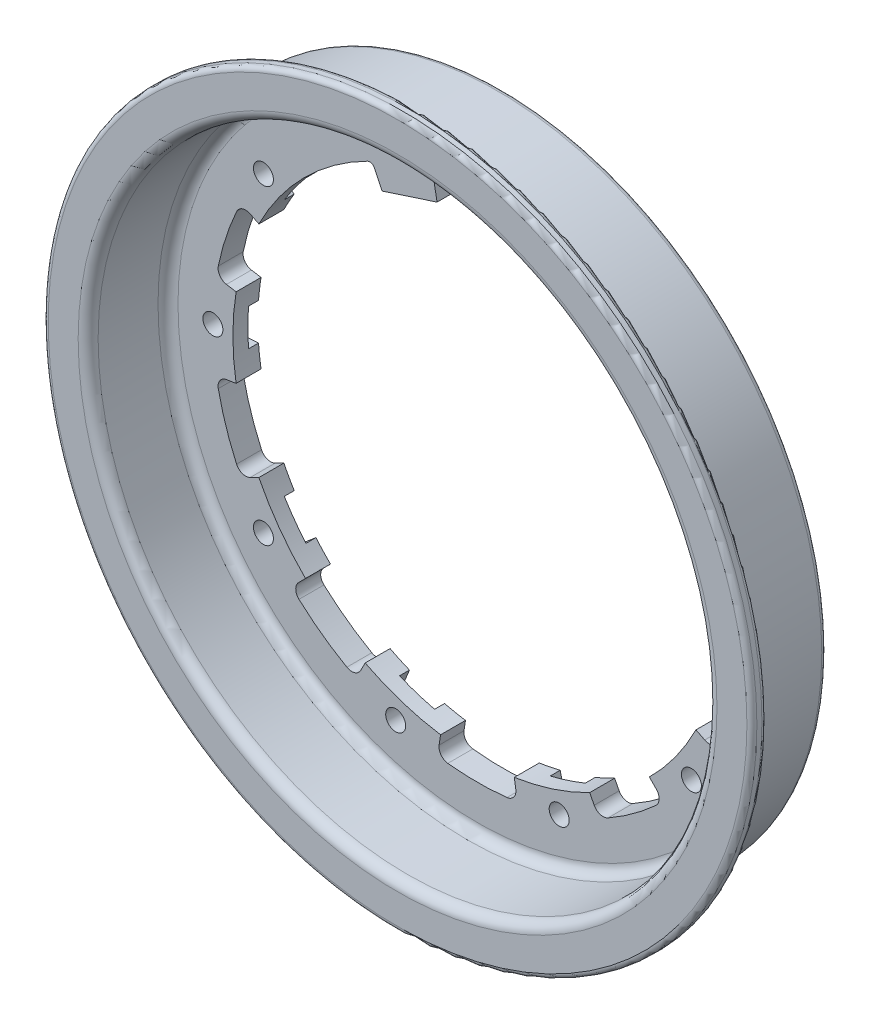
SolidWorks part; units mm, degrees
material "6061 合金"
ref_plane "前视基准面" through (0, 0, 0) normal (0, 0, 1) x (1, 0, 0)
ref_plane "上视基准面" through (0, 0, 0) normal (0, 1, 0) x (1, 0, 0)
ref_plane "右视基准面" through (0, 0, 0) normal (1, 0, 0) x (0, 0, -1)
sketch "草图2" plane through (0, 0, 0) normal (0, 0, 1) x (1, 0, 0)
  circle A0 centre (0, 0) radius 65 construction
  circle A1 centre (0, 0) radius 65 construction
  circle A2 centre (0, 0) radius 71
  circle A4 centre (0, 0) radius 62
  dimension "D1" = 6
  dimension "D3" = 3
extrude "凸台-拉伸1" add sketch "草图2" along normal blind 3
sketch "草图3" plane through (0, 0, 0) normal (0, 0, -1) x (-1, 0, 0)
  circle A0 centre (0, 0) radius 65 construction
  circle A1 centre (0, 0) radius 62 construction
  circle A2 centre (0, 0) radius 65
  circle A3 centre (0, 0) radius 62
  circle M3 centre (0, 0) radius 62
extrude "凸台-拉伸2" add sketch "草图3" along normal offset from surface (16 mm away) 3 contours A2 M3 region at (63.1615, 0, 0) offset beyond the face yes
sketch "草图4" plane through (0, 0, -13) normal (0, 0, -1) x (-1, 0, 0)
  circle A0 centre (0, 0) radius 53 construction
  circle A2 centre (0, 0) radius 65 construction
  circle A3 centre (0, 0) radius 65
  circle A4 centre (0, 0) radius 49
extrude "凸台-拉伸3" add sketch "草图4" along normal blind 5
fillet "圆角1" radius 2 1 edges at (-62, 0, -13)
fillet "圆角3" radius 2 1 edges at (62, 0, 3)
fillet "圆角4" radius 1 2 edges at (71, 0, 0) (71, 0, 3)
sketch "草图5" plane through (0, 0, 3) normal (0, 0, 1) x (1, 0, 0)
  circle A0 centre (42.8779, 31.1526) radius 2
  circle A1 centre (53, 0) radius 2
  circle A2 centre (42.8779, -31.1526) radius 2
  circle A3 centre (16.3779, -50.406) radius 2
  circle A4 centre (-16.3779, -50.406) radius 2
  circle A5 centre (-42.8779, -31.1526) radius 2
  circle A6 centre (-53, 0) radius 2
  circle A7 centre (-42.8779, 31.1526) radius 2
  circle A8 centre (-16.3779, 50.406) radius 2
  circle A9 centre (16.3779, 50.406) radius 2
  point P24 (0, 0)
  dimension "D1" = 10
extrude "切除-拉伸1" cut sketch "草图5" against normal through all both and the other way through all
ref_axis "基准轴1" through (-16.3779, 50.406, -18) along (0, 0, 1)
ref_axis "基准轴2" through (16.3779, -50.406, -18) along (0, 0, 1)
ref_plane "基准面1" through (0, 0, 0) normal (-0.9511, -0.309, 0) x (0, 0, 1)
ref_plane "基准面2" through (-16.3779, 50.406, 0) normal (0.309, -0.9511, 0) x (0, 0, 1)
sketch "草图8" plane through (-16.3779, 50.406, 0) normal (0.309, -0.9511, 0) x (0, 0, 1)
  line L0 (-19.6771, 0) -> (5.3103, 0) construction
  line L5 (-18, 4) -> (-13, 4)
  line L7 (-18, 4) -> (-18, -4)
  line L8 (-18, -4) -> (-13, -4)
  line L9 (-13, 4) -> (-13, -4)
  point P10 (-18, 0)
  point P11 (-13, 0)
  dimension "D1" = 4
  dimension "D2" = 5
sketch "草图9" plane through (0, 0, -13) normal (0, 0, 1) x (1, 0, 0)
  line L0 (-16.3779, 50.406) -> (0, 0) construction
  line L1 (-21.7113, 45.5187) -> (-9.1904, 49.587)
  line L2 (0, 0) -> (-9.1904, 49.587)
  line L3 (-8.0876, 43.6365) -> (-19.1059, 40.0564)
  line L4 (0, 0) -> (-21.7113, 45.5187)
  circle A1 centre (-16.3779, 50.406) radius 2 construction
  point P11 (-15.4508, 47.5528)
  point P12 (-13.5967, 41.8465)
  dimension "D1" = 7.5
  dimension "D2" = 3
  dimension "D3" = 9
extrude "凸台-拉伸5" add sketch "草图9" against normal blind 5 contours L0 L3 L2 | L0 L4 L3 region at (-14.5435, 44.7604, -13)
ref_axis "基准轴3" through (-16.3779, -50.406, -18) along (0, 0, 1)
ref_axis "基准轴4" through (16.3779, 50.406, -18) along (0, 0, 1)
ref_plane "基准面3" through (0, 0, 0) normal (0.9511, -0.309, 0) x (0, 0, -1)
fillet "圆角5" radius 1 1 edges at (-65, 0, -18)
sketch "草图17" plane through (0, 0, -18) normal (0, 0, -1) x (-1, 0, 0)
  line L0 (0, 0) -> (-20.078, 48.8863)
  line L1 (0, 0) -> (-12.4912, 51.3514)
  line L2 (0, 0) -> (20.078, 48.8863)
  line L3 (0, 0) -> (12.4912, 51.3514)
  line L4 (0, 0) -> (44.9781, 27.7483)
  line L5 (0, 0) -> (40.2892, 34.202)
  line L6 (0, 0) -> (52.6981, -3.9886)
  line L7 (0, 0) -> (52.6981, 3.9886)
  line L8 (0, 0) -> (40.2892, -34.202)
  line L9 (0, 0) -> (44.9781, -27.7483)
  line L10 (0, 0) -> (12.4912, -51.3514)
  line L11 (0, 0) -> (20.078, -48.8863)
  line L12 (0, 0) -> (-20.078, -48.8863)
  line L13 (0, 0) -> (-12.4912, -51.3514)
  line L14 (0, 0) -> (-44.9781, -27.7483)
  line L15 (0, 0) -> (-40.2892, -34.202)
  line L16 (0, 0) -> (-52.6981, 3.9886)
  line L17 (0, 0) -> (-52.6981, -3.9886)
  line L18 (0, 0) -> (-40.2892, 34.202)
  line L19 (0, 0) -> (-44.9781, 27.7483)
  arc A0 (-12.4912, 51.3514) -> (-20.078, 48.8863) centre (-16.3779, 50.406) ccw
  circle A10 centre (0, 0) radius 53 construction
  arc A11 (20.078, 48.8863) -> (12.4912, 51.3514) centre (16.3779, 50.406) ccw
  arc A12 (44.9781, 27.7483) -> (40.2892, 34.202) centre (42.8779, 31.1526) ccw
  arc A13 (52.6981, -3.9886) -> (52.6981, 3.9886) centre (53, 0) ccw
  arc A14 (40.2892, -34.202) -> (44.9781, -27.7483) centre (42.8779, -31.1526) ccw
  arc A15 (12.4912, -51.3514) -> (20.078, -48.8863) centre (16.3779, -50.406) ccw
  arc A16 (-20.078, -48.8863) -> (-12.4912, -51.3514) centre (-16.3779, -50.406) ccw
  arc A17 (-44.9781, -27.7483) -> (-40.2892, -34.202) centre (-42.8779, -31.1526) ccw
  arc A18 (-52.6981, 3.9886) -> (-52.6981, -3.9886) centre (-53, 0) ccw
  arc A19 (-40.2892, 34.202) -> (-44.9781, 27.7483) centre (-42.8779, 31.1526) ccw
  point P23 (0, 0)
  point P37 (0, 0)
  circle M8 centre (42.8779, 31.1526) radius 2
  circle M10 centre (42.8779, -31.1526) radius 2
  circle M11 centre (16.3779, -50.406) radius 2
  circle M12 centre (-16.3779, -50.406) radius 2
  circle M13 centre (-42.8779, -31.1526) radius 2
  circle M14 centre (-53, 0) radius 2
  circle M15 centre (-16.3779, 50.406) radius 2
  circle M16 centre (-42.8779, 31.1526) radius 2
  arc M17 (21.095, 44.2267) -> (8.9295, 48.1795) centre (0, 0) cw
  dimension "D1" = 10
extrude "切除-拉伸8" cut sketch "草图17" against normal blind 2 contours L1 A0 L0 M17 M15 | L18 A19 L19 M17 M16 | L16 A18 L17 M17 M14 | L14 A17 L15 M17 M13 | L12 A16 L13 M17 M12 | L10 A15 L11 M17 M11 | L8 A14 L9 M17 M10 | L4 A12 L5 M17 M8 | L7 A13 L6 region at (19.2299, 47.1542, -18) region at (-39.7502, 28.8802, -18) region at (-39.7502, -28.8802, -18) region at (-15.1809, -46.722, -18) region at (15.1809, -46.722, -18) region at (39.7502, -28.8802, -18) region at (49.1141, 0, -18) region at (39.7502, 28.8802, -18)
fillet "圆角9" radius 1 2 edges at (-21.095, 44.2267, -15.5) (-8.9295, 48.1795, -15.5)
sketch "草图19" plane through (0, 0, -18) normal (0, 0, -1) x (-1, 0, 0)
  line L0 (0, 0) -> (-24.9126, 48.2088)
  line L1 (0, 0) -> (-40.0409, 40.5024)
  line L3 (-37.3551, 31.7112) -> (-40.2892, 34.202) construction
  line L4 (-18.6158, 45.3261) -> (-20.078, 48.8863) construction
  circle A0 centre (0, 0) radius 53
  circle A1 centre (0, 0) radius 49
  arc M42 (-37.3551, 31.7112) -> (-18.6158, 45.3261) centre (0, 0) cw
  dimension "D3" = 106
  dimension "D1" = 5
  dimension "D2" = 5
extrude "切除-拉伸10" cut sketch "草图19" against normal blind 25 contours L0 A0 L1 M42 | L1 L0 M42 region at (19.1278, 26.3271, -18) region at (29.878, 41.1236, -18)
pattern_circular "阵列(圆周)2" count 10 over 360 about axis through (0, 0, -18) along (0, 0, -1) skipping 8, 9 of "切除-拉伸10"
fillet "圆角10" radius 2 16 edges at (-47.3605, 23.7905, -15.5) (-52.2991, 8.5909, -15.5) (-52.2991, -8.5909, -15.5) (-47.3605, -23.7905, -15.5) (-37.2613, -37.6908, -15.5) (-24.3317, -47.0847, -15.5) (-7.9909, -52.3941, -15.5) (7.9909, -52.3941, -15.5) (24.3317, -47.0847, -15.5) (37.2613, -37.6908, -15.5) (47.3605, -23.7905, -15.5) (52.2991, -8.5909, -15.5) (52.2991, 8.5909, -15.5) (47.3605, 23.7905, -15.5) (24.3317, 47.0847, -15.5) (37.2613, 37.6908, -15.5)
sketch "草图20" plane through (0, 0, -18) normal (0, 0, -1) x (-1, 0, 0)
  circle A0 centre (16.3779, 50.406) radius 4
extrude "切除-拉伸11" cut sketch "草图20" against normal blind 2
equation "\"8、\"=10"
